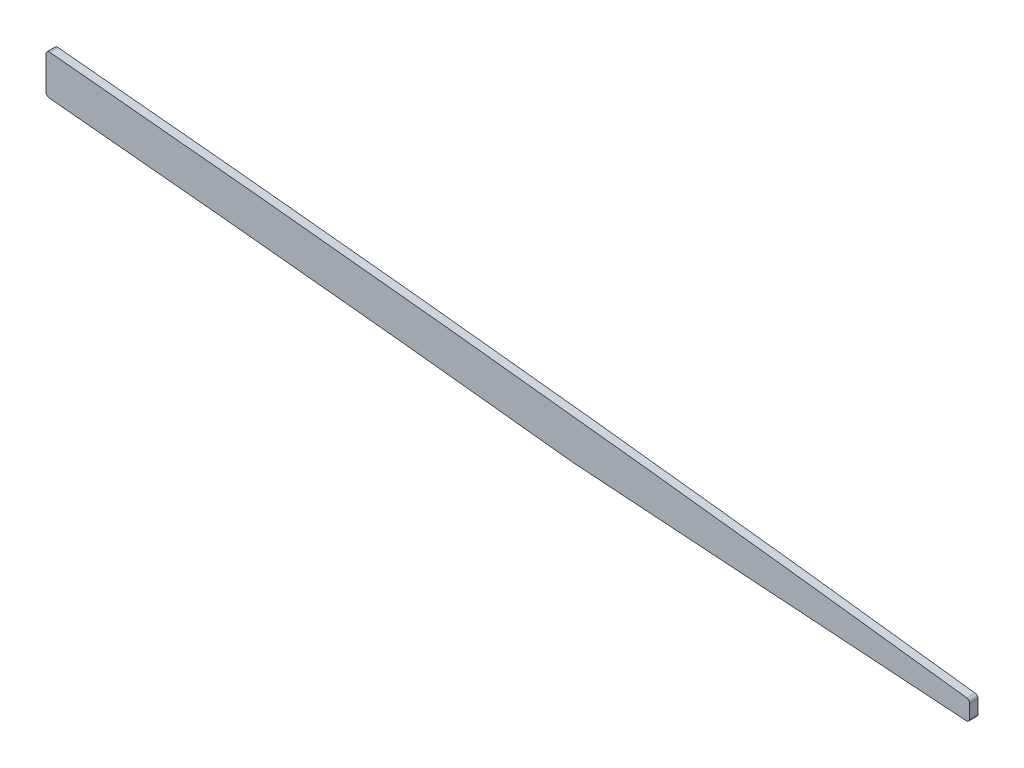
SolidWorks part; units mm, degrees
ref_plane "Front Plane" through (0, 0, 0) normal (0, 0, 1) x (1, 0, 0)
ref_plane "Top Plane" through (0, 0, 0) normal (0, 1, 0) x (1, 0, 0)
ref_plane "Right Plane" through (0, 0, 0) normal (1, 0, 0) x (0, 0, -1)
sketch "Sketch2" plane through (0, 0, 0) normal (0, 0, 1) x (1, 0, 0)
  line L0 (0, 0) -> (266.9553, 0) construction
  line L1 (825.5, 263.7287) -> (825.5, 174.6622)
  line L2 (2311.4, 135.8299) -> (2311.4, 52.664)
  line L3 (2665.4125, 96.9963) -> (2665.4125, 81.6353)
  line L4 (2665.4125, 89.3583) -> (2513.3711, 99.8062)
  spline S0 degree 5 poles (818.067, 264.7065) (827.0431, 263.4992) (836.0291, 262.3734) (845.0868, 261.3058) (891.3865, 256.087) (937.6862, 251.7792) (973.4521, 248.2277) (1071.9467, 239.0511) (1170.4413, 229.7315) (1231.7919, 224.5039) (1324.8993, 216.7906) (1418.0067, 209.0401) (1449.7429, 206.3618) (1636.9286, 190.5211) (1824.1143, 175.4092) (1979.9669, 164.2997) (2156.2686, 150.4144) (2332.5703, 133.8572) (2354.213, 131.7851) (2436.3555, 123.724) (2518.4981, 114.8591) (2579.4813, 107.7425) (2639.6368, 100.3834) (2699.7923, 92.6045) knots 77.930822 77.930822 77.930822 77.930822 77.930822 77.930822 82.465793 82.465793 82.465793 100.79329 100.79329 100.79329 131.098954 131.098954 131.098954 146.769198 146.769198 146.769198 223.533959 223.533959 223.533959 233.943117 233.943117 233.943117 264.216209 264.216209 264.216209 264.216209 264.216209 264.216209 weights 1 1 1 1 1 1 1 1 1 1 1 1 1 1 1 1 1 1 1 1 1 1 1 1
  spline S1 degree 1 poles (816.0355, 249.6025) (2697.8379, 77.4903) knots 0 0 1 1 construction
  spline S2 degree 3 poles (816.0355, 249.6025) (820.896, 248.9488) (830.6112, 247.6997) (845.2811, 245.9534) (860.0865, 244.2956) (879.8307, 242.1866) (904.37, 239.6983) (933.571, 236.8322) (962.6427, 234.0237) (991.7626, 231.242) (1021.072, 228.4759) (1060.3764, 224.797) (1109.513, 220.1844) (1168.5112, 214.8171) (1227.5001, 209.6621) (1306.1332, 203.0212) (1404.3615, 194.9207) (1522.2399, 184.9181) (1640.1829, 175.167) (1758.1654, 165.7576) (1876.1554, 156.5909) (1994.0875, 147.4533) (2092.2687, 139.6242) (2170.748, 133.0797) (2219.7717, 128.8422) (2258.984, 125.3472) (2288.3795, 122.6709) (2317.8122, 119.9317) (2347.5515, 117.1004) (2377.1599, 114.2101) (2406.4697, 111.269) (2435.8183, 108.2401) (2469.0247, 104.7153) (2497.3133, 101.6123) (2518.2453, 99.2591) (2543.5949, 96.3824) (2583.4681, 91.7389) (2626.5047, 86.5072) (2656.9573, 82.7047) (2676.2281, 80.2695) (2689.7296, 78.5389) (2697.8379, 77.4903) knots 77.930822 77.930822 77.930822 77.930822 79.386176 80.841531 82.296885 83.75224 86.662949 89.573658 92.484367 95.395077 98.305786 101.216495 107.037913 112.859332 118.68075 124.502168 136.145005 147.787842 159.430678 171.073515 182.716352 194.359189 206.002025 211.823444 217.644862 220.555571 223.46628 226.37699 229.287699 232.198408 235.109117 238.019826 240.930535 244.998119 246.453473 247.181151 252.573372 258.39479 260.13238 261.765912 264.216209 264.216209 264.216209 264.216209
  spline S3 degree 5 poles (818.067, -264.7065) (827.0431, -263.4992) (836.0291, -262.3734) (845.0868, -261.3058) (891.3865, -256.087) (937.6862, -251.7792) (973.4521, -248.2277) (1071.9467, -239.0511) (1170.4413, -229.7315) (1231.7919, -224.5039) (1324.8993, -216.7906) (1418.0067, -209.0401) (1449.7429, -206.3618) (1636.9286, -190.5211) (1824.1143, -175.4092) (1979.9669, -164.2997) (2156.2686, -150.4144) (2332.5703, -133.8572) (2354.213, -131.7851) (2436.3555, -123.724) (2518.4981, -114.8591) (2579.4813, -107.7425) (2639.6368, -100.3834) (2699.7923, -92.6045) knots 77.930822 77.930822 77.930822 77.930822 77.930822 77.930822 82.465793 82.465793 82.465793 100.79329 100.79329 100.79329 131.098954 131.098954 131.098954 146.769198 146.769198 146.769198 223.533959 223.533959 223.533959 233.943117 233.943117 233.943117 264.216209 264.216209 264.216209 264.216209 264.216209 264.216209 weights 1 1 1 1 1 1 1 1 1 1 1 1 1 1 1 1 1 1 1 1 1 1 1 1
  point P2 (0, 0)
  dimension "D1" = 818.067
  dimension "D2" = 825.5
  dimension "D3" = 2311.4
  dimension "D5" = 2665.4125
  dimension "D6" = 7.62
  dimension "D7" = 152.4
  dimension "D4" = 15.24
extrude "Boss-Extrude1" add sketch "Sketch2" along normal mid plane 3.175 contours L2 S2 L3 S0 region at (2473.8425, 111.9714, 0)
fillet "Fillet1" radius 1.27 4 edges at (2311.4, 120.5233, 0) (2665.4125, 89.3583, 0)
